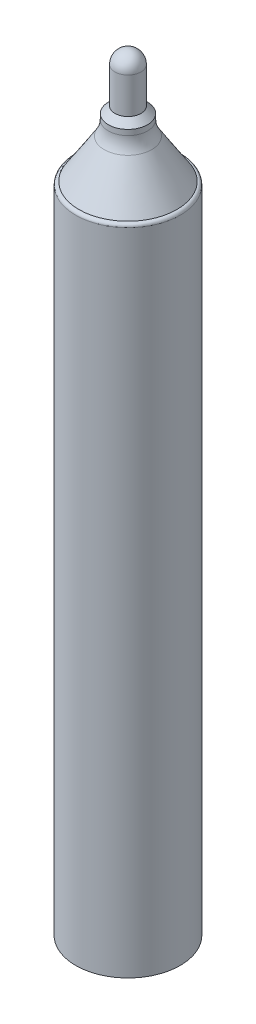
SolidWorks part; units mm, degrees
ref_plane "前视基准面" through (0, 0, 0) normal (0, 0, 1) x (1, 0, 0)
ref_plane "上视基准面" through (0, 0, 0) normal (0, 1, 0) x (1, 0, 0)
ref_plane "右视基准面" through (0, 0, 0) normal (1, 0, 0) x (0, 0, -1)
other "Configuration Table"
sketch "草图1" plane through (0, 0, 0) normal (0, 1, 0) x (1, 0, 0)
  circle A0 centre (0, 0) radius 8
  dimension "D1" = 16
extrude "凸台-拉伸1" add sketch "草图1" along normal blind 100
sketch "草图2" plane through (0, 0, 0) normal (0, 0, 1) x (1, 0, 0)
  line L0 (0, 100) -> (0, 0) construction
  line L1 (8, 100) -> (-8, 100) construction
  line L2 (-8, 0) -> (8, 0) construction
  line L3 (0, 100) -> (0, 110)
  line L4 (0, 110) -> (3, 110)
  line L5 (3, 110) -> (3, 107)
  line L6 (3, 107) -> (7.5, 100)
  line L7 (7.5, 100) -> (0, 100)
  dimension "D1" = 7.5
  dimension "D2" = 3
  dimension "D3" = 3
  dimension "D4" = 10
revolve "旋转1" add sketch "草图2" angle 360 about L0
fillet "圆角1" radius 0.5 1 edges at (0, 100, 8)
fillet "圆角2" radius 4 1 edges at (-3, 107, 0)
sketch "草图3" plane through (0, 0, 0) normal (0, 0, 1) x (1, 0, 0)
  line L0 (0, 110) -> (0, 0) construction
  line L1 (3, 110) -> (-3, 110) construction
  line L2 (-8, 0) -> (8, 0) construction
  line L3 (0, 110) -> (0, 117.5)
  line L4 (2, 115.5) -> (2, 110)
  line L6 (2, 110) -> (0, 110)
  arc A0 (2, 115.5) -> (0, 117.5) centre (0, 115.5) ccw
  dimension "D1" = 4
  dimension "D2" = 7.5
revolve "旋转2" add sketch "草图3" angle 360 about L0
chamfer "倒角1" distance 1 angle 45 1 edges at (-3, 110, 0)
